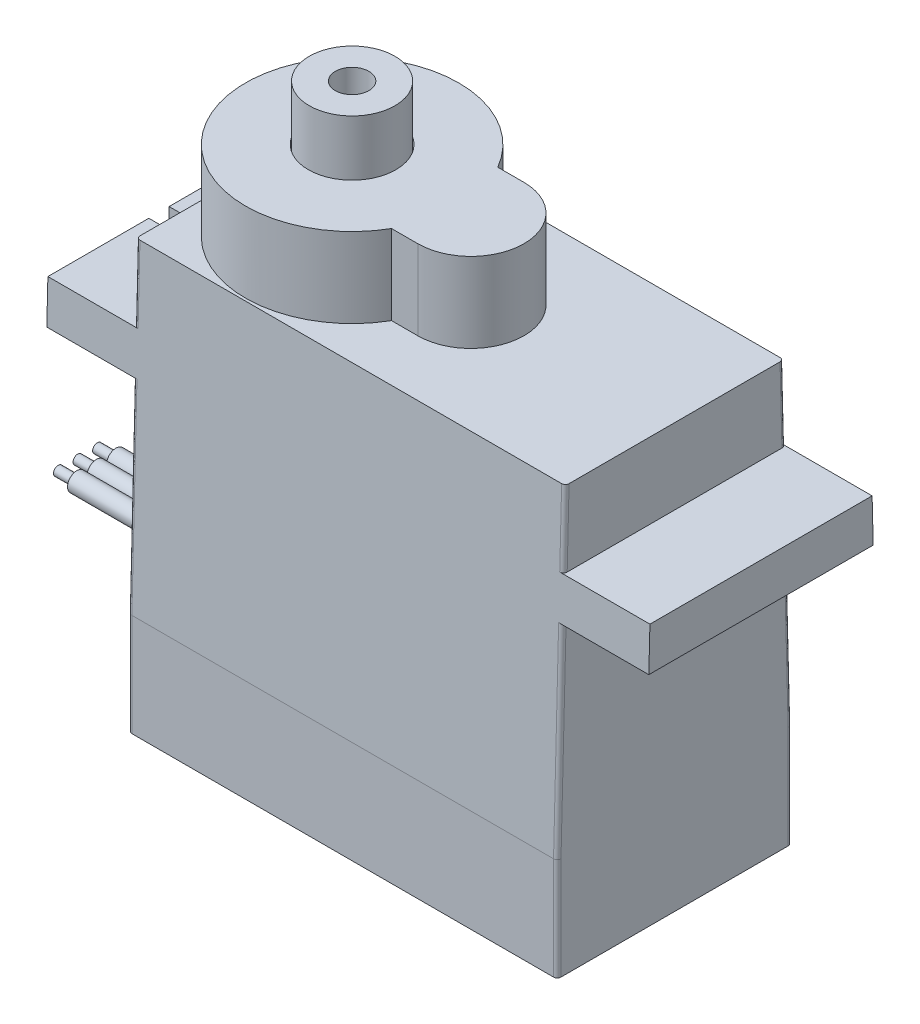
SolidWorks part; units mm, degrees
ref_plane "Front Plane" through (0, 0, 0) normal (0, 0, 1) x (1, 0, 0)
ref_plane "Top Plane" through (0, 0, 0) normal (0, 1, 0) x (1, 0, 0)
ref_plane "Right Plane" through (0, 0, 0) normal (1, 0, 0) x (0, 0, -1)
ref_axis "X-Axis" through (-88.99, 0, 0) along (1, 0, 0)
ref_axis "Y-Axis" through (0, 0, -88.99) along (0, 0, 1)
ref_axis "Z-Axis" through (0, 55, 0) along (0, -1, 0)
sketch "Sketch1" plane through (0, 0, 0) normal (0, 0, 1) x (1, 0, 0)
  line L0 (0, 0) -> (0, 12.96) construction
  line L1 (-7.13, 6.38) -> (15.9, 6.38)
  line L2 (-7.13, 6.38) -> (-7.13, 2.32)
  line L3 (-7.13, -16.34) -> (15.9, -16.34)
  line L4 (15.9, 6.38) -> (15.9, 2.32)
  line L5 (15.9, 2.32) -> (20.54, 2.32)
  line L6 (-11.77, 2.32) -> (-7.13, 2.32)
  line L7 (-11.77, 2.32) -> (-11.77, 0)
  line L8 (-11.77, 0) -> (-7.13, 0)
  line L9 (20.54, 2.32) -> (20.54, 0)
  line L10 (15.9, 0) -> (20.54, 0)
  line L11 (-7.13, 0) -> (-7.13, -16.34)
  line L12 (15.9, 0) -> (15.9, -16.34)
  line L14 (15.9, 0) -> (-7.13, 0) construction
  point P3 (4.385, 0)
  dimension "D1" = 2.32
  dimension "D2" = 32.31
  dimension "D3" = 23.03
  dimension "D4" = 16.34
  dimension "D5" = 22.72
  dimension "D6" = 7.13
  dimension "D7" = 15.9
  dimension "D10" = 29.3
  dimension "D11" = 4.385
extrude "Boss-Extrude1" add sketch "Sketch1" along normal mid plane 12.59
sketch "Sketch2" plane through (0, 6.38, 0) normal (0, 1, 0) x (1, 0, 0)
  line L0 (-1.405, 0) -> (4.97, 0) construction
  line L1 (3.5602, -2.85) -> (4.97, -2.85)
  line L2 (4.97, 2.85) -> (3.5602, 2.85)
  line L3 (-1.405, 0) -> (-7.13, 0) construction
  line L4 (4.97, 0) -> (7.82, 0) construction
  line L5 (-7.13, -6.295) -> (-7.13, 6.295) construction
  arc A0 (3.5602, 2.85) -> (3.5602, -2.85) centre (-1.405, 0) ccw
  arc A1 (4.97, -2.85) -> (4.97, 2.85) centre (4.97, 0) ccw
  dimension "D1" = 11.45
  dimension "D2" = 5.7
  dimension "D3" = 14.95
extrude "Boss-Extrude2" add sketch "Sketch2" along normal blind 4.28
sketch "Sketch11" plane through (-11.77, 0, 0) normal (-1, 0, 0) x (0, 0, 1)
  line L0 (-5.86, 6.38) -> (-6.295, -10.84)
  line L1 (0, 6.38) -> (-6.295, 6.38) construction
  line L2 (6.295, -16.34) -> (-6.295, -16.34) construction
  line L3 (-6.295, 0) -> (-6.295, -16.34) construction
  line L4 (-5.86, 6.38) -> (-6.295, 6.38)
  line L5 (-6.295, 6.38) -> (-6.295, -10.84)
  dimension "D1" = 5.86
  dimension "D2" = 5.5
extrude "Cut-Extrude4" cut sketch "Sketch11" against normal through all
mirror "Mirror1" about plane through (0, 0, 0) normal (0, 0, 1) of "Cut-Extrude4"
sketch "Sketch4" plane through (0, 0, 0) normal (0, 1, 0) x (1, 0, 0)
  line L0 (-7.13, 0) -> (-9.45, 0) construction
  line L1 (-11.77, -5.9626) -> (-11.77, 5.9626) construction
  line L2 (-10.2585, 0.545) -> (-11.77, 0.545)
  line L3 (-10.2585, 0.545) -> (-10.2585, -0.545)
  line L4 (-10.2585, -0.545) -> (-11.77, -0.545)
  line L5 (-11.77, 0.545) -> (-11.77, -0.545)
  line L8 (-9.45, 0) -> (-10.2585, 0) construction
  line L9 (-9.45, 0) -> (-11.77, 0) construction
  arc A0 (3.5602, 2.85) -> (3.5602, -2.85) centre (-1.405, 0) ccw construction
  circle A1 centre (-9.45, 0) radius 0.975
  dimension "D1" = 1.09
  dimension "D2" = 1.95
extrude "Cut-Extrude1" cut sketch "Sketch4" along normal through all contours A1 | L4 L5 L2 L3
sketch "Sketch5" plane through (0, -16.34, 0) normal (0, -1, 0) x (1, 0, 0)
  line L0 (15.9, 6.295) -> (-7.13, -6.295) construction
  line L17 (-5.49, 4.35) -> (14.26, 4.35) construction
  line L18 (-5.49, 4.35) -> (-5.49, -4.35) construction
  line L19 (-5.49, -4.35) -> (14.26, -4.35) construction
  line L20 (14.26, 4.35) -> (14.26, -4.35) construction
  line L21 (-5.49, 4.35) -> (14.26, -4.35) construction
  circle A0 centre (-5.49, 4.35) radius 1
  circle A1 centre (-5.49, -4.35) radius 1
  circle A2 centre (14.26, -4.35) radius 1
  circle A3 centre (14.26, 4.35) radius 1
  circle A4 centre (-5.49, 4.35) radius 0.975
  circle A5 centre (-5.49, -4.35) radius 0.975
  circle A6 centre (14.26, -4.35) radius 0.975
  circle A7 centre (14.26, 4.35) radius 0.975
  point P36 (4.385, 0)
  dimension "D1" = 0.025
  dimension "D4" = 1.95
  dimension "D5" = 19.75
  dimension "D6" = 8.7
extrude "Cut-Extrude2" cut sketch "Sketch5" against normal blind 1
sketch "Sketch6" plane through (-7.13, 0, 0) normal (-1, 0, 0) x (0, 0, 1)
  line L0 (-1.05, -11.34) -> (1.05, -11.34) construction
  line L1 (0, -11.84) -> (0, -16.34) construction
  line L3 (6.295, -16.34) -> (-6.295, -16.34) construction
  circle A0 centre (0, -11.34) radius 0.5
  circle A1 centre (1.05, -11.34) radius 0.5
  circle A2 centre (-1.05, -11.34) radius 0.5
  dimension "D3" = 1
  dimension "D1" = 4.5
  dimension "D2" = 2.1
extrude "Boss-Extrude4" add sketch "Sketch6" along normal blind 8
sketch "Sketch7" plane through (-15.13, 0, 0) normal (-1, 0, 0) x (0, 0, 1)
  circle A0 centre (0, -11.34) radius 0.25
  circle A1 centre (1.05, -11.34) radius 0.25
  circle A2 centre (-1.05, -11.34) radius 0.25
  dimension "D1" = 0.5
extrude "Boss-Extrude5" add sketch "Sketch7" along normal blind 1
sketch "Sketch3" plane through (0, 10.66, 0) normal (0, 1, 0) x (1, 0, 0)
  line L0 (4.7718, -0.52) -> (4.97, -0.52)
  line L1 (4.97, 0.52) -> (4.7718, 0.52)
  line L2 (5.49, 0) -> (7.82, 0) construction
  line L3 (-4.8, 0) -> (-7.13, 0) construction
  arc A0 (4.7718, 0.52) -> (4.7718, -0.52) centre (0, 0) ccw
  arc A1 (4.97, -0.52) -> (4.97, 0.52) centre (4.97, 0) ccw
  arc A2 (4.97, -2.85) -> (4.97, 2.85) centre (4.97, 0) ccw construction
  arc A3 (3.5602, 2.85) -> (3.5602, -2.85) centre (-1.405, 0) ccw construction
  dimension "D1" = 9.6
fillet "Fillet1" radius 0.3 4 edges at (14.26, -16.34, -5.325) (14.26, -16.34, 3.375) (-5.49, -16.34, -5.325) (-5.49, -16.34, 3.375)
fillet "Fillet3" radius 0.2 12 edges at (15.9, -13.59, -6.295) (15.9, -13.59, 6.295) (-7.13, -13.59, -6.295) (-7.13, -13.59, 6.295) (-7.13, -5.42, 6.1581) (-7.13, -5.42, -6.1581) (15.9, -5.42, 6.1581) (15.9, -5.42, -6.1581) (15.9, 4.35, -5.9113) (15.9, 4.35, 5.9113) (-7.13, 4.35, -5.9113) (-7.13, 4.35, 5.9113)
sketch "Sketch12" plane through (0, 10.66, 0) normal (0, 1, 0) x (1, 0, 0)
  circle A0 centre (-1.405, 0) radius 2.3
  circle A1 centre (-1.405, 0) radius 0.9
  dimension "D1" = 4.6
  dimension "D2" = 1.8
extrude "Boss-Extrude6" add sketch "Sketch12" along normal blind 2.95 and the other way blind 1 separate body
sketch "Sketch13" plane through (0, 13.61, 0) normal (0, 1, 0) x (1, 0, 0)
  circle A0 centre (-1.405, 0) radius 2.35
  dimension "D1" = 4.7
extrude "Cut-Extrude5" cut sketch "Sketch13" against normal blind 5
